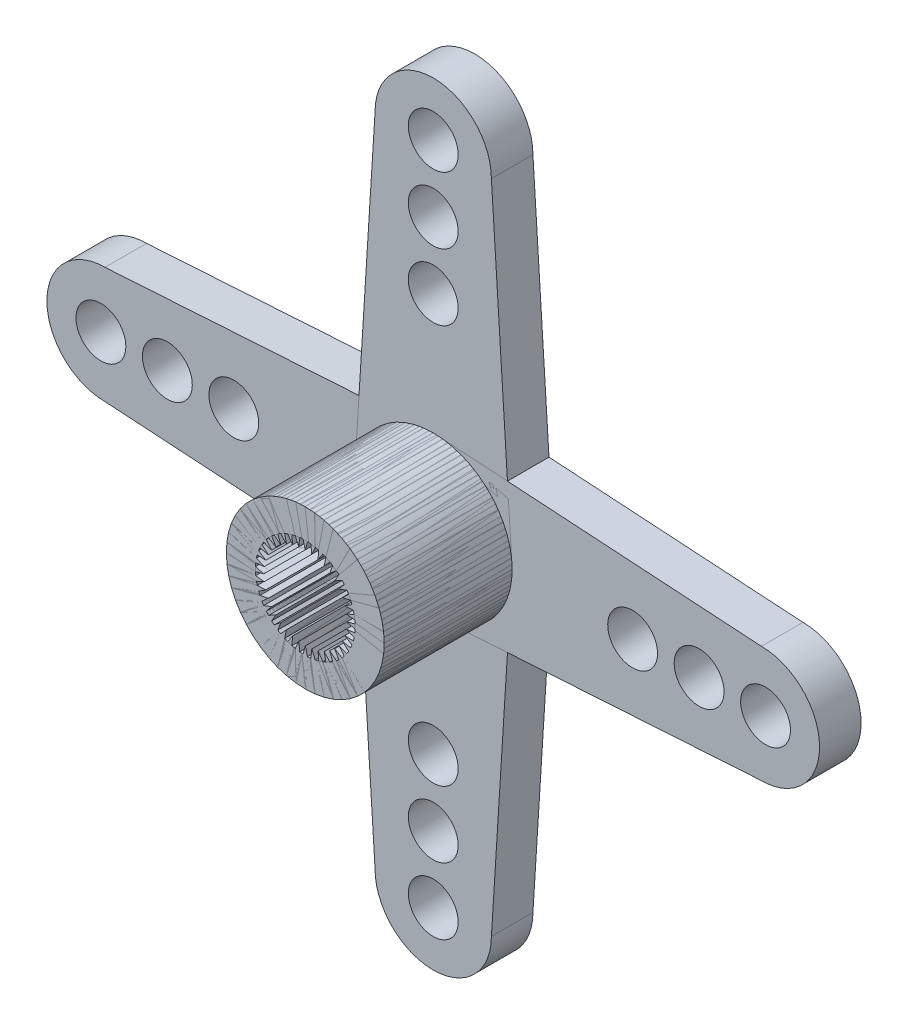
SolidWorks part; units mm, degrees
ref_plane "Front Plane" through (0, 0, 0) normal (0, 0, 1) x (1, 0, 0)
ref_plane "Top Plane" through (0, 0, 0) normal (0, 1, 0) x (1, 0, 0)
ref_plane "Right Plane" through (0, 0, 0) normal (1, 0, 0) x (0, 0, -1)
sketch "Sketch1" plane through (0, 0, 0) normal (0, 0, 1) x (1, 0, 0)
  line L0 (-2.9388, 0.6027) -> (-2.4692, 0.3911)
  line L1 (-2.4692, 0.3911) -> (-2.9812, 0.335)
  line L2 (-2.9969, 0.1355) -> (-2.5, 0)
  line L3 (-2.5, 0) -> (-2.9969, -0.1355)
  line L4 (-2.9812, -0.335) -> (-2.4692, -0.3911)
  line L5 (-2.4692, -0.3911) -> (-2.9388, -0.6027)
  line L6 (-2.8921, -0.7972) -> (-2.3776, -0.7725)
  line L7 (-2.3776, -0.7725) -> (-2.8084, -1.055)
  line L8 (-2.7318, -1.2398) -> (-2.2275, -1.135)
  line L9 (-2.2275, -1.135) -> (-2.6088, -1.4813)
  line L10 (-2.5042, -1.6519) -> (-2.0225, -1.4695)
  line L11 (-2.0225, -1.4695) -> (-2.3449, -1.8712)
  line L12 (-2.215, -2.0233) -> (-1.7678, -1.7678)
  line L13 (-1.7678, -1.7678) -> (-2.0233, -2.215)
  line L14 (-1.8712, -2.3449) -> (-1.4695, -2.0225)
  line L15 (-1.4695, -2.0225) -> (-1.6519, -2.5042)
  line L16 (-1.4813, -2.6088) -> (-1.135, -2.2275)
  line L17 (-1.135, -2.2275) -> (-1.2398, -2.7318)
  line L18 (-1.055, -2.8084) -> (-0.7725, -2.3776)
  line L19 (-0.7725, -2.3776) -> (-0.7972, -2.8921)
  line L20 (-0.6027, -2.9388) -> (-0.3911, -2.4692)
  line L21 (-0.3911, -2.4692) -> (-0.335, -2.9812)
  line L22 (-0.1355, -2.9969) -> (0, -2.5)
  line L23 (0, -2.5) -> (0.1355, -2.9969)
  line L24 (0.335, -2.9812) -> (0.3911, -2.4692)
  line L25 (0.3911, -2.4692) -> (0.6027, -2.9388)
  line L26 (0.7972, -2.8921) -> (0.7725, -2.3776)
  line L27 (0.7725, -2.3776) -> (1.055, -2.8084)
  line L28 (1.2398, -2.7318) -> (1.135, -2.2275)
  line L29 (1.135, -2.2275) -> (1.4813, -2.6088)
  line L30 (1.6519, -2.5042) -> (1.4695, -2.0225)
  line L31 (1.4695, -2.0225) -> (1.8712, -2.3449)
  line L32 (2.0233, -2.215) -> (1.7678, -1.7678)
  line L33 (1.7678, -1.7678) -> (2.215, -2.0233)
  line L34 (2.3449, -1.8712) -> (2.0225, -1.4695)
  line L35 (2.0225, -1.4695) -> (2.5042, -1.6519)
  line L36 (2.6088, -1.4813) -> (2.2275, -1.135)
  line L37 (2.2275, -1.135) -> (2.7318, -1.2398)
  line L38 (2.8084, -1.055) -> (2.3776, -0.7725)
  line L39 (2.3776, -0.7725) -> (2.8921, -0.7972)
  line L40 (2.9388, -0.6027) -> (2.4692, -0.3911)
  line L41 (2.4692, -0.3911) -> (2.9812, -0.335)
  line L42 (2.9969, -0.1355) -> (2.5, 0)
  line L43 (2.5, 0) -> (2.9969, 0.1355)
  line L44 (2.9812, 0.335) -> (2.4692, 0.3911)
  line L45 (2.4692, 0.3911) -> (2.9388, 0.6027)
  line L46 (2.8921, 0.7972) -> (2.3776, 0.7725)
  line L47 (2.3776, 0.7725) -> (2.8084, 1.055)
  line L48 (2.7318, 1.2398) -> (2.2275, 1.135)
  line L49 (2.2275, 1.135) -> (2.6088, 1.4813)
  line L50 (2.5042, 1.6519) -> (2.0225, 1.4695)
  line L51 (2.0225, 1.4695) -> (2.3449, 1.8712)
  line L52 (2.215, 2.0233) -> (1.7678, 1.7678)
  line L53 (1.7678, 1.7678) -> (2.0233, 2.215)
  line L54 (1.8712, 2.3449) -> (1.4695, 2.0225)
  line L55 (1.4695, 2.0225) -> (1.6519, 2.5042)
  line L56 (1.4813, 2.6088) -> (1.135, 2.2275)
  line L57 (1.135, 2.2275) -> (1.2398, 2.7318)
  line L58 (1.055, 2.8084) -> (0.7725, 2.3776)
  line L59 (0.7725, 2.3776) -> (0.7972, 2.8921)
  line L60 (0.6027, 2.9388) -> (0.3911, 2.4692)
  line L61 (0.3911, 2.4692) -> (0.335, 2.9812)
  line L62 (0.1355, 2.9969) -> (0, 2.5)
  line L63 (0, 2.5) -> (-0.1355, 2.9969)
  line L64 (-0.335, 2.9812) -> (-0.3911, 2.4692)
  line L65 (-0.3911, 2.4692) -> (-0.6027, 2.9388)
  line L66 (-0.7972, 2.8921) -> (-0.7725, 2.3776)
  line L67 (-0.7725, 2.3776) -> (-1.055, 2.8084)
  line L68 (-1.2398, 2.7318) -> (-1.135, 2.2275)
  line L69 (-1.135, 2.2275) -> (-1.4813, 2.6088)
  line L70 (-1.6519, 2.5042) -> (-1.4695, 2.0225)
  line L71 (-1.4695, 2.0225) -> (-1.8712, 2.3449)
  line L72 (-2.0233, 2.215) -> (-1.7678, 1.7678)
  line L73 (-1.7678, 1.7678) -> (-2.215, 2.0233)
  line L74 (-2.3449, 1.8712) -> (-2.0225, 1.4695)
  line L75 (-2.0225, 1.4695) -> (-2.5042, 1.6519)
  line L76 (-2.6088, 1.4813) -> (-2.2275, 1.135)
  line L77 (-2.2275, 1.135) -> (-2.7318, 1.2398)
  line L78 (-2.8084, 1.055) -> (-2.3776, 0.7725)
  line L79 (-2.3776, 0.7725) -> (-2.8921, 0.7972)
  arc A0 (-2.9812, 0.335) -> (-2.9969, 0.1355) centre (0, 0) ccw
  arc A1 (-2.9969, -0.1355) -> (-2.9812, -0.335) centre (0, 0) ccw
  arc A2 (-2.9388, -0.6027) -> (-2.8921, -0.7972) centre (0, 0) ccw
  arc A3 (-2.8084, -1.055) -> (-2.7318, -1.2398) centre (0, 0) ccw
  arc A4 (-2.6088, -1.4813) -> (-2.5042, -1.6519) centre (0, 0) ccw
  arc A5 (-2.3449, -1.8712) -> (-2.215, -2.0233) centre (0, 0) ccw
  arc A6 (-2.0233, -2.215) -> (-1.8712, -2.3449) centre (0, 0) ccw
  arc A7 (-1.6519, -2.5042) -> (-1.4813, -2.6088) centre (0, 0) ccw
  arc A8 (-1.2398, -2.7318) -> (-1.055, -2.8084) centre (0, 0) ccw
  arc A9 (-0.7972, -2.8921) -> (-0.6027, -2.9388) centre (0, 0) ccw
  arc A10 (-0.335, -2.9812) -> (-0.1355, -2.9969) centre (0, 0) ccw
  arc A11 (0.1355, -2.9969) -> (0.335, -2.9812) centre (0, 0) ccw
  arc A12 (0.6027, -2.9388) -> (0.7972, -2.8921) centre (0, 0) ccw
  arc A13 (1.055, -2.8084) -> (1.2398, -2.7318) centre (0, 0) ccw
  arc A14 (1.4813, -2.6088) -> (1.6519, -2.5042) centre (0, 0) ccw
  arc A15 (1.8712, -2.3449) -> (2.0233, -2.215) centre (0, 0) ccw
  arc A16 (2.215, -2.0233) -> (2.3449, -1.8712) centre (0, 0) ccw
  arc A17 (2.5042, -1.6519) -> (2.6088, -1.4813) centre (0, 0) ccw
  arc A18 (2.7318, -1.2398) -> (2.8084, -1.055) centre (0, 0) ccw
  arc A19 (2.8921, -0.7972) -> (2.9388, -0.6027) centre (0, 0) ccw
  arc A20 (2.9812, -0.335) -> (2.9969, -0.1355) centre (0, 0) ccw
  arc A21 (2.9969, 0.1355) -> (2.9812, 0.335) centre (0, 0) ccw
  arc A22 (2.9388, 0.6027) -> (2.8921, 0.7972) centre (0, 0) ccw
  arc A23 (2.8084, 1.055) -> (2.7318, 1.2398) centre (0, 0) ccw
  arc A24 (2.6088, 1.4813) -> (2.5042, 1.6519) centre (0, 0) ccw
  arc A25 (2.3449, 1.8712) -> (2.215, 2.0233) centre (0, 0) ccw
  arc A26 (2.0233, 2.215) -> (1.8712, 2.3449) centre (0, 0) ccw
  arc A27 (1.6519, 2.5042) -> (1.4813, 2.6088) centre (0, 0) ccw
  arc A28 (1.2398, 2.7318) -> (1.055, 2.8084) centre (0, 0) ccw
  arc A29 (0.7972, 2.8921) -> (0.6027, 2.9388) centre (0, 0) ccw
  arc A30 (0.335, 2.9812) -> (0.1355, 2.9969) centre (0, 0) ccw
  arc A31 (-0.1355, 2.9969) -> (-0.335, 2.9812) centre (0, 0) ccw
  arc A32 (-0.6027, 2.9388) -> (-0.7972, 2.8921) centre (0, 0) ccw
  arc A33 (-1.055, 2.8084) -> (-1.2398, 2.7318) centre (0, 0) ccw
  arc A34 (-1.4813, 2.6088) -> (-1.6519, 2.5042) centre (0, 0) ccw
  arc A35 (-1.8712, 2.3449) -> (-2.0233, 2.215) centre (0, 0) ccw
  arc A36 (-2.215, 2.0233) -> (-2.3449, 1.8712) centre (0, 0) ccw
  arc A37 (-2.5042, 1.6519) -> (-2.6088, 1.4813) centre (0, 0) ccw
  arc A38 (-2.7318, 1.2398) -> (-2.8084, 1.055) centre (0, 0) ccw
  arc A39 (-2.8921, 0.7972) -> (-2.9388, 0.6027) centre (0, 0) ccw
  circle A40 centre (0, 0) radius 3
sketch "Sketch2" plane through (0, 0, 0) normal (0, 0, 1) x (1, 0, 0)
  line L0 (-12.25, 0) -> (12.25, 0) construction
  line L1 (0, 12.25) -> (0, -12.25) construction
  circle A0 centre (0, 0) radius 12.25
  circle A2 centre (0, 8.25) radius 1.5944
  circle A3 centre (0, -8.25) radius 1.5944
  circle A4 centre (-8.25, 0) radius 1.5944
  circle A5 centre (8.25, 0) radius 1.5944
  dimension "D1" = 16.5
  dimension "D2" = 24.5
  dimension "D3" = 16.5
  dimension "D4" = 8.25
  dimension "D5" = 8.25
extrude "Boss-Extrude1" add sketch "Sketch2" along normal blind 1
sketch "Sketch3" plane through (0, 0, 1) normal (0, 0, 1) x (1, 0, 0)
  circle A0 centre (0, 0) radius 1.5
extrude "Cut-Extrude1" cut sketch "Sketch3" against normal blind 2
sketch "Sketch4" plane through (0, 0, 1) normal (0, 0, 1) x (1, 0, 0)
  circle A0 centre (0, 0) radius 3
  circle A1 centre (0, 0) radius 4
extrude "Boss-Extrude2" add sketch "Sketch4" along normal blind 5.7
extrude "Boss-Extrude3" add sketch "Sketch1" along normal blind 5.7 from surface contours L2 A40 L3 | L0 A40 L1 | L78 A40 L79 | L76 A40 L77 | L74 A40 L75 | L72 A40 L73 | L70 A40 L71 | L68 A40 L69 | L66 A40 L67 | L64 A40 L65 | L62 A40 L63 | L60 A40 L61 | L58 A40 L59 | L56 A40 L57 | L54 A40 L55 | L52 A40 L53 | L50 A40 L51 | L48 A40 L49 | L46 A40 L47 | L44 A40 L45 | L42 A40 L43 | L40 A40 L41 | L38 A40 L39 | L36 A40 L37 | L34 A40 L35 | L32 A40 L33 | L30 A40 L31 | L28 A40 L29 | L26 A40 L27 | L24 A40 L25 | L22 A40 L23 | L20 A40 L21 | L18 A40 L19 | L16 A40 L17 | L14 A40 L15 | L12 A40 L13 | L10 A40 L11 | L8 A40 L9 | L6 A40 L7 | L4 A40 L5 region at (-2.7978, 0.4431, 0) region at (-2.694, 0.8753, 0) region at (-2.8327, 0, 0) region at (-2.5239, 1.286, 0) region at (-2.7978, -0.4431, 0) region at (-2.2917, 1.665, 0) region at (-2.694, -0.8753, 0) region at (-2.003, 2.003, 0) region at (-2.5239, -1.286, 0) region at (-1.665, 2.2917, 0) region at (-2.2917, -1.665, 0) region at (-1.286, 2.5239, 0) region at (-2.003, -2.003, 0) region at (-0.8753, 2.694, 0) region at (-1.665, -2.2917, 0) region at (-0.4431, 2.7978, 0) region at (-1.286, -2.5239, 0) region at (0, 2.8327, 0) region at (-0.8753, -2.694, 0) region at (0.4431, 2.7978, 0) region at (-0.4431, -2.7978, 0) region at (0.8753, 2.694, 0) region at (0, -2.8327, 0) region at (1.286, 2.5239, 0) region at (0.4431, -2.7978, 0) region at (1.665, 2.2917, 0) region at (0.8753, -2.694, 0) region at (2.003, 2.003, 0) region at (1.286, -2.5239, 0) region at (2.2917, 1.665, 0) region at (1.665, -2.2917, 0) region at (2.5239, 1.286, 0) region at (2.003, -2.003, 0) region at (2.694, 0.8753, 0) region at (2.2917, -1.665, 0) region at (2.7978, 0.4431, 0) region at (2.5239, -1.286, 0) region at (2.8327, 0, 0) region at (2.694, -0.8753, 0) region at (2.7978, -0.4431, 0) starting at face at (1.5, 0, 1)
sketch "Sketch5" plane through (0, 0, 0) normal (0, 0, -1) x (-1, 0, 0)
  circle A0 centre (0, 0) radius 3
  point P4 (0, 0)
extrude "Cut-Extrude2" cut sketch "Sketch5" against normal blind 0.5
sketch "Sketch6" plane through (0, 0, 1) normal (0, 0, 1) x (1, 0, 0)
  circle A0 centre (0, 0) radius 4.25
  circle A1 centre (0, 0) radius 12.25
extrude "Cut-Extrude3" cut sketch "Sketch6" against normal blind 10
sketch "Sketch7" plane through (0, 0, 1) normal (0, 0, 1) x (1, 0, 0)
  circle A1 centre (0, 0) radius 4.25
  circle A2 centre (0, 0) radius 4.25
  circle M2 centre (0, 0) radius 4
  circle M3 centre (0, 0) radius 4.25
  dimension "D1" = 0
extrude "Boss-Extrude5" add sketch "Sketch7" along normal up to surface (5.7 mm away) contours M3 M2 region at (-4.1298, 0, 1) up to face at (4, 0, 6.7)
sketch "Sketch8" plane through (0, 0, 0) normal (0, 0, -1) x (-1, 0, 0)
  circle A0 centre (0, 0) radius 4.25 construction
  circle A1 centre (0, 0) radius 4.25
  circle A2 centre (0, 0) radius 4.75
extrude "Boss-Extrude6" add sketch "Sketch8" against normal up to surface (6.7 mm away) up to face at (0, 0, 6.7)
sketch "Sketch9" plane through (0, 0, 0) normal (0, 0, -1) x (-1, 0, 0)
  circle A0 centre (0, 0) radius 3
  circle A1 centre (0, 0) radius 4.75
extrude "Boss-Extrude7" add sketch "Sketch9" along normal blind 3.5
sketch "Sketch11" plane through (0, 0, -3.5) normal (0, 0, -1) x (-1, 0, 0)
  line L0 (0, 0) -> (0, -19.75) construction
  line L1 (-4.75, 0) -> (-3.5, -19.75)
  line L2 (4.75, 0) -> (3.5, -19.75)
  line L3 (0, 4.75) -> (0, -23.25) construction
  arc A1 (-3.5, -19.75) -> (3.5, -19.75) centre (0, -19.75) ccw
  circle A2 centre (0, 0) radius 4.75 construction
  arc A3 (-4.75, 0) -> (4.75, 0) centre (0, 0) ccw
  circle A5 centre (0, -16) radius 1.5
  circle A6 centre (0, -12) radius 1.5
  circle A7 centre (0, -20) radius 1.5
  point P1 (0, -23.25)
  point P3 (0, 4.75)
  circle M4 centre (0, 0) radius 4.75
  dimension "D1" = 3.5
  dimension "D2" = 28
  dimension "D3" = 20
  dimension "D4" = 16
  dimension "D5" = 12
extrude "Boss-Extrude8" add sketch "Sketch11" against normal blind 2.5 contours L1 A1 L2 A7 A6 A5 M4 region at (0, -4.9953, -3.5)
chamfer "Chamfer3" distance 0.5 angle 45 1 edges at (-3, 0, -3.5)
ref_axis "ServoAxis" through (0, 0, 0.5) along (0, 0, 1)
pattern_circular "CirPattern2" count 4 every 90 about axis through (0, 0, 6.7) along (0, 0, -1) of bodies 111
